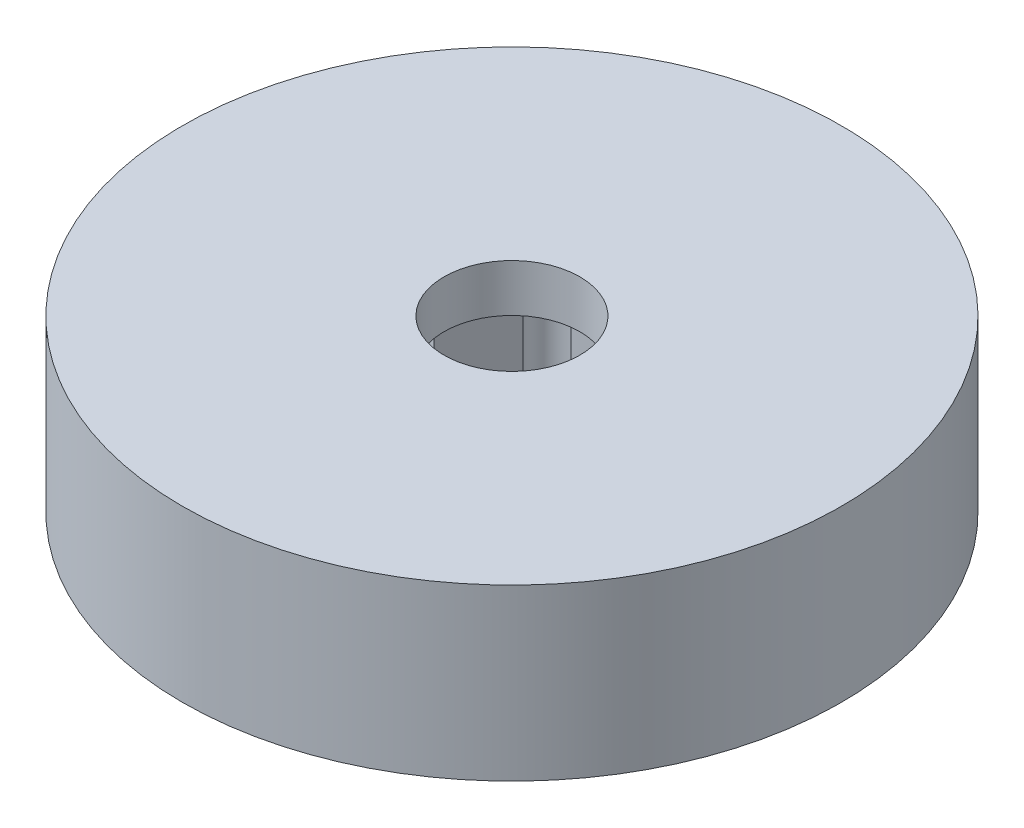
SolidWorks part; units mm, degrees
ref_plane "Front Plane" through (0, 0, 0) normal (0, 0, 1) x (1, 0, 0)
ref_plane "Top Plane" through (0, 0, 0) normal (0, 1, 0) x (1, 0, 0)
ref_plane "Right Plane" through (0, 0, 0) normal (1, 0, 0) x (0, 0, -1)
sketch "Sketch1" plane through (0, 0, 0) normal (0, 1, 0) x (1, 0, 0)
  circle A0 centre (0, 0) radius 24.257
  dimension "D1" = 48.514
extrude "Boss-Extrude1" add sketch "Sketch1" along normal blind 12.5
hole_wizard "Ø10.0mm Dowel Hole1" positions "Sketch3" profile "Sketch2" hole size "Ø10.0" standard "ANSI Metric" end condition through all
sketch "Sketch3" plane through (0, 0, 0) normal (0, -1, 0) x (-1, 0, 0)
  point P0 (0, 0)
sketch "Sketch2" plane through (0, 0, 0) normal (1, 0, 0) x (0, 0, -1)
  line L0 (0, 0) -> (0, 12.5)
  line L1 (0, 12.5) -> (5, 12.5)
  line L2 (5, 12.5) -> (5, 0)
  line L5 (5, 0) -> (0, 0)
  line L11 (0, -6.35) -> (0, 107.95) construction
  dimension "Thru Hole Dia." = 10
  dimension "Thru Hole Depth" = 12.5
sketch "Sketch4" plane through (0, 0, 0) normal (0, -1, 0) x (-1, 0, 0)
  line L1 (-3.8971, -6.75) -> (3.8971, -6.75)
  line L2 (3.8971, -6.75) -> (7.7942, 0)
  line L3 (7.7942, 0) -> (3.8971, 6.75)
  line L4 (3.8971, 6.75) -> (-3.8971, 6.75)
  line L5 (-3.8971, 6.75) -> (-7.7942, 0)
  line L6 (-7.7942, 0) -> (-3.8971, -6.75)
  circle A0 centre (0, 0) radius 6.75 construction
  dimension "D1" = 13.5
extrude "Cut-Extrude1" cut sketch "Sketch4" against normal blind 9
sketch "Sketch5" plane through (0, 0, 0) normal (0, -1, 0) x (1, 0, 0)
  circle A1 centre (-7.7942, 0) radius 1.5
  circle A2 centre (0, 0) radius 34.257
  circle A3 centre (0, 0) radius 34.257
  circle A4 centre (-3.8971, 6.75) radius 1.5
  circle A5 centre (3.8971, 6.75) radius 1.5
  circle A6 centre (7.7942, 0) radius 1.5
  circle A7 centre (3.8971, -6.75) radius 1.5
  circle A8 centre (-3.8971, -6.75) radius 1.5
  line M2 (-3.8971, 6.75) -> (3.8971, 6.75)
  line M3 (3.8971, 6.75) -> (7.7942, 0)
  line M4 (7.7942, 0) -> (3.8971, -6.75)
  line M5 (3.8971, -6.75) -> (-3.8971, -6.75)
  line M6 (-3.8971, -6.75) -> (-7.7942, 0)
  line M7 (-7.7942, 0) -> (-3.8971, 6.75)
  dimension "D2" = 3
  dimension "D3" = 3
  dimension "D4" = 3
  dimension "D5" = 3
  dimension "D6" = 3
  dimension "D7" = 3
  dimension "D1" = 10
extrude "Cut-Extrude3" cut sketch "Sketch5" against normal blind 10 contours A8 M6 M5 | A1 M7 M6 | A4 M2 M7 | A5 M3 M2 | A6 M4 M3 | A7 M5 M4 region at (-8.2077, 0, 0) region at (-4.1039, 0, 7.1081) region at (-4.1039, 0, -7.1081) region at (4.1039, 0, 7.1081) region at (4.1039, 0, -7.1081) region at (8.2077, 0, 0)
